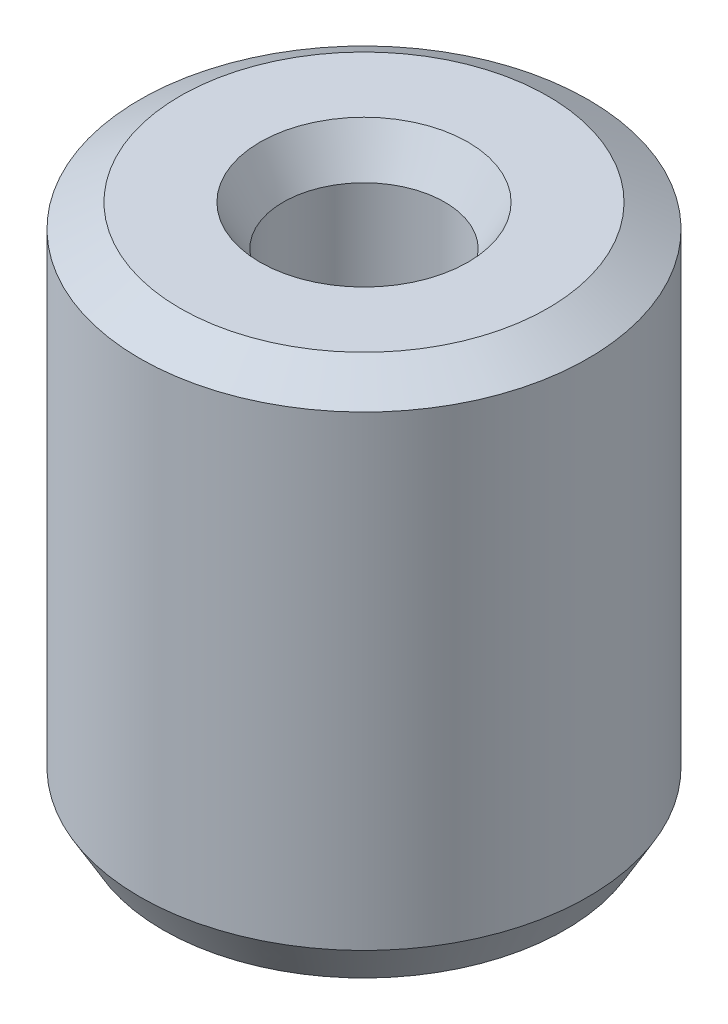
SolidWorks part; units mm, degrees
ref_plane "Front Plane" through (0, 0, 0) normal (0, 0, 1) x (1, 0, 0)
ref_plane "Top Plane" through (0, 0, 0) normal (0, 1, 0) x (1, 0, 0)
ref_plane "Right Plane" through (0, 0, 0) normal (1, 0, 0) x (0, 0, -1)
sketch "Sketch1" plane through (0, 0, 0) normal (0, 1, 0) x (1, 0, 0)
  circle A0 centre (0, 0) radius 12.5
  dimension "SLEEVE_OD" = 25
extrude "Boss-Extrude1" add sketch "Sketch1" along normal blind 29.5413
sketch "Sketch2" plane through (0, 0, 0) normal (0, 1, 0) x (1, 0, 0)
  circle A0 centre (0, 0) radius 4.5027
  dimension "BORE_D" = 9.0055
extrude "Cut-Extrude1" cut sketch "Sketch2" along normal through all
chamfer "Chamfer1" distance 1.2973 angle 60 4 edges at (0, 29.5413, 4.5027) (0, 0, 4.5027) (0, 0, 12.5) (0, 29.5413, 12.5) first distance on face at (0, 29.5413, 4.5027) first distance on face at (0, 0, 4.5027) first distance on face at (0, 29.5413, 12.5)
